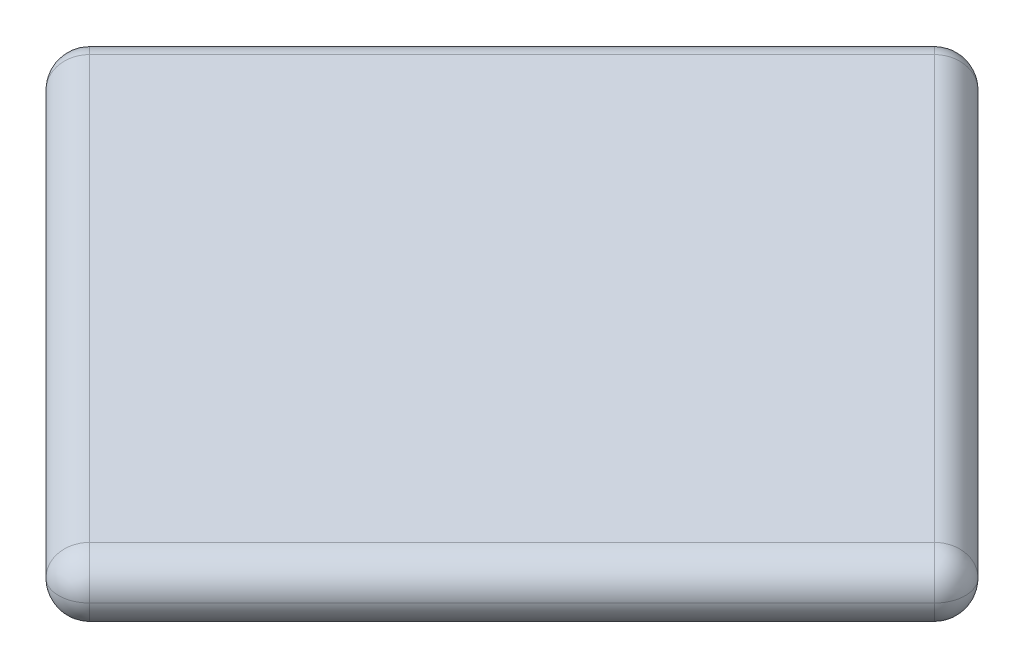
SolidWorks part; units mm, degrees
ref_plane "Front Plane" through (0, 0, 0) normal (0, 0, 1) x (1, 0, 0)
ref_plane "Top Plane" through (0, 0, 0) normal (0, 1, 0) x (1, 0, 0)
ref_plane "Right Plane" through (0, 0, 0) normal (1, 0, 0) x (0, 0, -1)
sketch "Sketch1" plane through (0, 0, 0) normal (0, 1, 0) x (1, 0, 0)
  line L1 (-14.1421, 288.7009) -> (-288.7009, 14.1421)
  line L2 (-288.7009, -14.1421) -> (-14.1421, -288.7009)
  line L3 (14.1421, -288.7009) -> (288.7009, -14.1421)
  line L4 (288.7009, 14.1421) -> (14.1421, 288.7009)
  circle A0 centre (0, 0) radius 214.1423 construction
  arc A1 (288.7009, -14.1421) -> (288.7009, 14.1421) centre (274.5587, 0) ccw
  arc A2 (-14.1421, -288.7009) -> (14.1421, -288.7009) centre (0, -274.5587) ccw
  arc A3 (-288.7009, 14.1421) -> (-288.7009, -14.1421) centre (-274.5587, 0) ccw
  arc A4 (-14.1421, 288.7009) -> (14.1421, 288.7009) centre (0, 274.5587) cw
  point P0 (302.843, 0)
  point P1 (0, -302.843)
  point P2 (-302.843, 0)
  point P3 (0, 302.843)
  dimension "D1" = 20
extrude "Boss-Extrude1" add sketch "Sketch1" along normal blind 20 and the other way blind 20
fillet "Fillet1" radius 20 16 edges at (151.4215, -20, 151.4215) (0, -20, 294.5587) (-151.4215, -20, 151.4215) (-294.5587, -20, 0) (-151.4215, -20, -151.4215) (0, -20, -294.5587) (151.4215, -20, -151.4215) (294.5587, -20, 0) (151.4215, 20, 151.4215) (0, 20, 294.5587) (-151.4215, 20, 151.4215) (-294.5587, 20, 0) (-151.4215, 20, -151.4215) (0, 20, -294.5587) (151.4215, 20, -151.4215) (294.5587, 20, 0)
